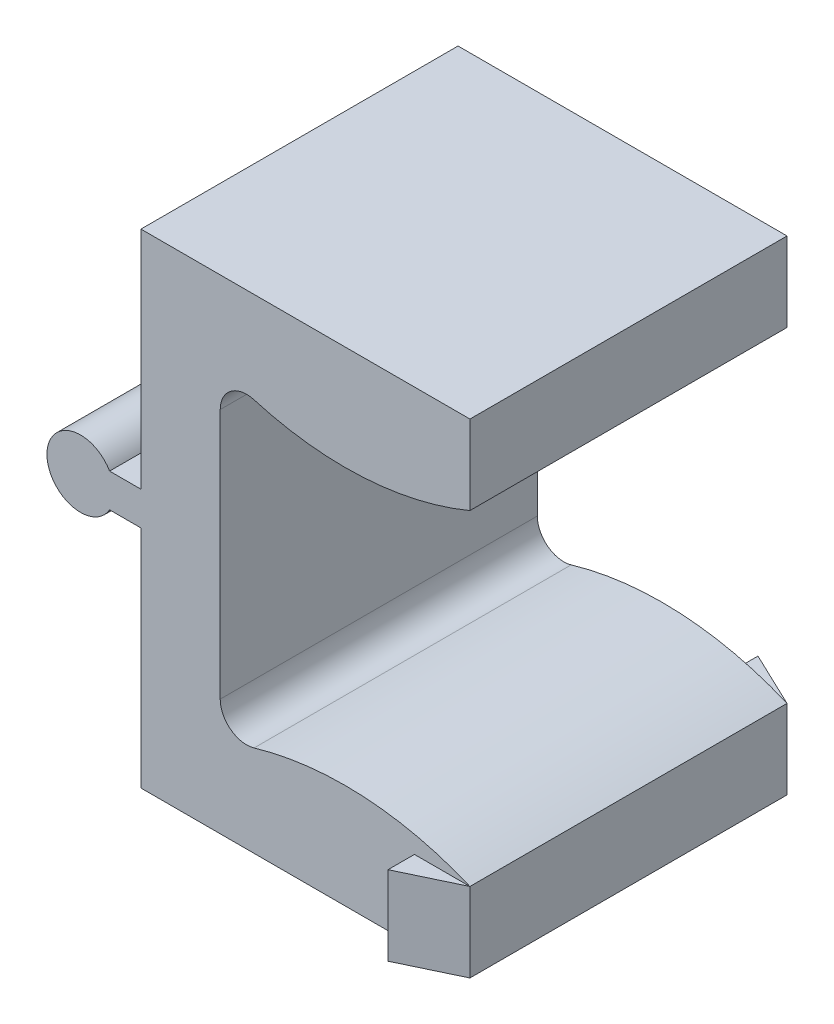
SolidWorks part; units mm, degrees
ref_plane "Front Plane" through (0, 0, 0) normal (0, 0, 1) x (1, 0, 0)
ref_plane "Top Plane" through (0, 0, 0) normal (0, 1, 0) x (1, 0, 0)
ref_plane "Right Plane" through (0, 0, 0) normal (1, 0, 0) x (0, 0, -1)
sketch "Sketch1" plane through (0, 0, 0) normal (0, 0, 1) x (1, 0, 0)
  line L2 (-159.7982, 9.1594) -> (-172.2482, 9.1594)
  line L3 (-172.2482, 9.1594) -> (-172.2482, -9.1594)
  line L7 (-169.2482, -22.8519) -> (-169.2482, 6.1594) construction
  line L13 (-142.8048, 5.1594) -> (-142.8048, -5.1594) construction
  line L23 (-159.7982, 6.1594) -> (-159.7982, 9.1594)
  line L28 (-164.5232, 5.2094) -> (-144.5007, 5.2094) construction
  line L30 (-169.2482, 6.1594) -> (-169.2482, 5.1594)
  line L34 (-169.2482, 5.1594) -> (-169.2482, -5.1594)
  line L35 (-172.2482, 0) -> (-169.2482, 0) construction
  line L36 (-169.2482, -6.1594) -> (-169.2482, -5.1594)
  line L37 (-159.7982, -6.1594) -> (-159.7982, -9.1594)
  line L38 (-159.7982, -9.1594) -> (-172.2482, -9.1594)
  arc A5 (-169.2482, 6.1594) -> (-159.7982, 6.1594) centre (-164.5232, 17.4347) ccw
  arc A6 (-169.2482, -6.1594) -> (-159.7982, -6.1594) centre (-164.5232, -17.4347) cw
  point P30 (-142.8048, 0)
  dimension "D6" = 12.2253
  dimension "D4" = 3
  dimension "D3" = 3
  dimension "D2" = 1
  dimension "D1" = 18.3188
  dimension "D5" = 12.45
extrude "MainBody" add sketch "Sketch1" along normal mid plane 12
sketch "Sketch3" plane through (0, -9.1594, 0) normal (0, -1, 0) x (1, 0, 0)
  line L0 (-159.7982, -6) -> (-161.8982, -7)
  line L1 (-161.8982, -7) -> (-161.8982, -6)
  line L2 (-172.2482, -6) -> (-159.7982, -6) construction
  line L3 (-161.8982, -6) -> (-159.7982, -6)
  line L5 (8.8033, 0) -> (-8.8033, 0) construction
  line L6 (-161.8982, 6) -> (-159.7982, 6)
  line L7 (-161.8982, 7) -> (-161.8982, 6)
  line L8 (-159.7982, 6) -> (-161.8982, 7)
  dimension "D1" = 2.1
  dimension "D2" = 1
extrude "Hook" add sketch "Sketch3" against normal up to vertex (3 mm away) up to point (-159.7982, -6.1594, -6)
fillet "Fillet2" radius 1 2 edges at (-169.2482, 6.1594, 0) (-169.2482, -6.1594, 0)
sketch "Sketch5" [suppressed] plane through (-172.2482, 0, 0) normal (-1, 0, 0) x (0, 0, 1)
  line L1 (-6, 9.1594) -> (6, 9.1594)
  line L2 (-6, 9.1594) -> (-6, -9.1594)
  line L3 (-6, -9.1594) -> (6, -9.1594)
  line L4 (6, 9.1594) -> (6, -9.1594)
extrude "Boss-Extrude1" [suppressed] add sketch "Sketch5" along normal blind 15
sketch "Sketch6" [suppressed] plane through (0, 9.1594, 0) normal (0, 1, 0) x (1, 0, 0)
  line L0 (-187.2482, -6) -> (-187.2482, 6) construction
  circle A0 centre (-182.2482, 0) radius 3.302
  dimension "D1" = 6.604
  dimension "D2" = 5
extrude "Cut-Extrude2" [suppressed] cut sketch "Sketch6" against normal through all
sketch "Sketch7" plane through (-172.2482, 0, 0) normal (-1, 0, 0) x (0, 0, 1)
  circle A0 centre (0, 0) radius 38.1
  dimension "D1" = 76.2
extrude "Boss-Extrude2" [suppressed] add sketch "Sketch7" along normal blind 5
fillet "Fillet3" [suppressed] radius 1
sketch "Sketch8" plane through (0, 0, 6) normal (0, 0, 1) x (1, 0, 0)
  line L6 (-172.2482, -0.635) -> (-173.4343, -0.635)
  line L8 (-172.2482, 0.635) -> (-173.4343, 0.635)
  line L10 (-172.2482, 0.635) -> (-173.4343, 0.635)
  line L11 (-172.2482, 0.635) -> (-172.2482, -0.635)
  line L12 (-161.8982, -9.1594) -> (-161.8982, -6.1594)
  line L14 (-169.2482, -4.7448) -> (-169.2482, 4.7448)
  line L15 (-159.7982, 6.1594) -> (-159.7982, 9.1594)
  line L16 (-159.7982, 9.1594) -> (-172.2482, 9.1594)
  line L17 (-172.2482, 9.1594) -> (-172.2482, -9.1594)
  line L18 (-172.2482, -9.1594) -> (-161.8982, -9.1594)
  line L21 (-169.2482, -4.7448) -> (-169.2482, 4.7448)
  line L22 (-159.7982, 6.1594) -> (-159.7982, 9.1594)
  line L23 (-159.7982, 9.1594) -> (-172.2482, 9.1594)
  line L24 (-172.2482, 9.1594) -> (-172.2482, -9.1594)
  line L25 (-172.2482, -9.1594) -> (-161.8982, -9.1594)
  line L26 (-172.2482, -0.635) -> (-173.4343, -0.635)
  line L32 (-161.8982, -9.1594) -> (-161.8982, -6.1594)
  line L33 (-161.8982, -6.1594) -> (-159.7982, -6.1594)
  line L34 (-161.8982, -6.1594) -> (-159.7982, -6.1594)
  arc A0 (-173.4343, 0.635) -> (-173.4343, -0.635) centre (-174.5342, 0) ccw
  arc A4 (-159.7982, -6.1594) -> (-167.9665, -5.7043) centre (-164.5232, -17.4347) ccw
  arc A6 (-169.2482, -4.7448) -> (-167.9665, -5.7043) centre (-168.2482, -4.7448) ccw
  arc A7 (-167.9665, 5.7043) -> (-159.7982, 6.1594) centre (-164.5232, 17.4347) ccw
  arc A8 (-159.7982, -6.1594) -> (-167.9665, -5.7043) centre (-164.5232, -17.4347) ccw
  arc A11 (-167.9665, 5.7043) -> (-159.7982, 6.1594) centre (-164.5232, 17.4347) ccw
  arc A12 (-169.2482, -4.7448) -> (-167.9665, -5.7043) centre (-168.2482, -4.7448) ccw
  arc A13 (-167.9665, 5.7043) -> (-169.2482, 4.7448) centre (-168.2482, 4.7448) ccw
  arc A14 (-167.9665, 5.7043) -> (-169.2482, 4.7448) centre (-168.2482, 4.7448) ccw
  point P6 (-172.2482, 0)
  line M14 (-172.2482, 9.1594) -> (-172.2482, -9.1594)
  dimension "D2" = 1.27
  dimension "D1" = 0
  dimension "D3" = 2.286
extrude "Slot" add sketch "Sketch8" against normal up to surface (12 mm away) contours L8 A0 L6 M14 region at (-174.164, 0, 6) up to face at (-165.6835, -0.5599, -6)
sketch "Sketch10" [suppressed] plane through (0, 0, -6) normal (0, 0, -1) x (-1, 0, 0)
  line L0 (166.0232, -9.1594) -> (172.2482, -9.1594)
  line L3 (172.2482, -9.1594) -> (166.0232, -9.1594)
  line L5 (172.2482, -9.1594) -> (187.9767, -44.4861)
  line L6 (195.4932, -61.3685) -> (192.3182, -61.3685)
  line L7 (159.7982, -6.1594) -> (159.7982, -9.1594)
  line L8 (159.7982, -6.1594) -> (159.7982, -9.1594)
  line L9 (159.7982, -9.1594) -> (172.2482, -9.1594)
  line L10 (172.2482, -9.1594) -> (172.2482, 9.1594)
  line L11 (172.2482, 9.1594) -> (159.7982, 9.1594)
  line L12 (159.7982, 9.1594) -> (159.7982, 6.1594)
  line L13 (169.2482, 6.1594) -> (169.2482, -6.1594)
  line L16 (159.7982, -9.1594) -> (172.2482, -9.1594)
  line L17 (172.2482, -9.1594) -> (172.2482, 9.1594)
  line L18 (172.2482, 9.1594) -> (159.7982, 9.1594)
  line L19 (159.7982, 9.1594) -> (159.7982, 6.1594)
  line L20 (169.2482, 6.1594) -> (169.2482, -6.1594)
  line L21 (195.4932, -61.3685) -> (201.8432, -61.3685)
  line L22 (201.8432, -61.3685) -> (201.8432, -59.781)
  line L24 (192.666, -55.0185) -> (200.9772, -55.0185)
  line L25 (169.0732, -9.1594) -> (192.3182, -61.3685)
  line L28 (201.8432, -59.781) -> (194.7864, -59.781)
  line L31 (193.3728, -56.606) -> (200.9772, -56.606)
  line L42 (200.9772, -55.0185) -> (200.9772, -56.606)
  line L43 (187.9767, -44.4861) -> (195.4932, -61.3685)
  arc A4 (169.2482, -6.1594) -> (159.7982, -6.1594) centre (164.5232, -17.4347) ccw
  arc A5 (159.7982, 6.1594) -> (169.2482, 6.1594) centre (164.5232, 17.4347) ccw
  arc A8 (169.2482, -6.1594) -> (159.7982, -6.1594) centre (164.5232, -17.4347) ccw
  arc A9 (159.7982, 6.1594) -> (169.2482, 6.1594) centre (164.5232, 17.4347) ccw
  dimension "D5" = 6.35
  dimension "D7" = 3.175
  dimension "D8" = 3.175
  dimension "D2" = 57.15
  dimension "D10" = 1.5875
  dimension "D13" = 114
  dimension "D14" = 114
  dimension "D3" = 1.5875
  dimension "D4" = 3.175
extrude "Boss-Extrude3" [suppressed] add sketch "Sketch10" against normal up to surface (12 mm away) up to face at (-167.7502, -0.4106, 6)
sketch "Sketch11" [suppressed] plane through (0, 0, -6) normal (0, 0, -1) x (-1, 0, 0)
  line L0 (159.7982, -9.1594) -> (159.7982, 9.1594)
  line L11 (169.2482, 6.1594) -> (169.2482, -6.1594)
  line L12 (159.7982, -6.1594) -> (159.7982, -9.1594)
  line L13 (159.7982, -9.1594) -> (169.0732, -9.1594)
  line L14 (169.0732, -9.1594) -> (192.3182, -61.3685)
  line L15 (192.3182, -61.3685) -> (201.8432, -61.3685)
  line L16 (201.8432, -61.3685) -> (201.8432, -59.781)
  line L17 (201.8432, -59.781) -> (194.7864, -59.781)
  line L18 (194.7864, -59.781) -> (193.3728, -56.606)
  line L19 (172.2482, -9.1594) -> (172.2482, 9.1594)
  line L20 (172.2482, 9.1594) -> (159.7982, 9.1594)
  line L21 (159.7982, 9.1594) -> (159.7982, 6.1594)
  line L22 (169.2482, 6.1594) -> (169.2482, -6.1594)
  line L23 (159.7982, -6.1594) -> (159.7982, -9.1594)
  line L24 (159.7982, -9.1594) -> (169.0732, -9.1594)
  line L25 (169.0732, -9.1594) -> (192.3182, -61.3685)
  line L26 (192.3182, -61.3685) -> (201.8432, -61.3685)
  line L27 (201.8432, -61.3685) -> (201.8432, -59.781)
  line L28 (201.8432, -59.781) -> (194.7864, -59.781)
  line L29 (194.7864, -59.781) -> (193.3728, -56.606)
  line L30 (172.2482, -9.1594) -> (172.2482, 9.1594)
  line L31 (172.2482, 9.1594) -> (159.7982, 9.1594)
  line L32 (159.7982, 9.1594) -> (159.7982, 6.1594)
  line L37 (193.3728, -56.606) -> (200.9772, -56.606)
  line L38 (193.3728, -56.606) -> (200.9772, -56.606)
  line L39 (200.9772, -56.606) -> (200.9772, -55.0185)
  line L40 (200.9772, -56.606) -> (200.9772, -55.0185)
  line L41 (192.666, -55.0185) -> (172.2482, -9.1594)
  line L42 (192.666, -55.0185) -> (172.2482, -9.1594)
  line L44 (200.9772, -55.0185) -> (192.666, -55.0185)
  line L45 (200.9772, -55.0185) -> (192.666, -55.0185)
  arc A2 (159.7982, 6.1594) -> (169.2482, 6.1594) centre (164.5232, 17.4347) ccw
  arc A3 (169.2482, -6.1594) -> (159.7982, -6.1594) centre (164.5232, -17.4347) ccw
  arc A4 (159.7982, 6.1594) -> (169.2482, 6.1594) centre (164.5232, 17.4347) ccw
  arc A5 (169.2482, -6.1594) -> (159.7982, -6.1594) centre (164.5232, -17.4347) ccw
  dimension "D1" = 0
extrude "Boss-Extrude4" [suppressed] add sketch "Sketch11" against normal up to surface (12 mm away) up to face at (-167.7502, -0.4106, 6)
sketch "Sketch12" [suppressed] plane through (0, 0, -6) normal (0, 0, -1) x (-1, 0, 0)
  line L0 (159.7982, -9.1594) -> (159.7982, -5.9844)
  line L1 (159.7982, -5.9844) -> (162.0842, -5.9844)
  line L3 (162.0842, -5.2351) -> (159.7982, -5.2351)
  line L4 (162.0842, -5.2351) -> (162.0842, -6.7337)
  line L5 (162.0842, -6.7337) -> (159.7982, -6.7337)
  line L6 (159.7982, -5.2351) -> (159.7982, -6.7337)
  line L7 (162.0842, -5.2351) -> (159.7982, -6.7337) construction
  line L8 (162.0842, -6.7337) -> (159.7982, -5.2351) construction
  line L9 (172.2482, 9.1594) -> (159.7982, 9.1594)
  line L10 (159.7982, 9.1594) -> (159.7982, -9.1594)
  line L11 (159.7982, -9.1594) -> (169.0732, -9.1594)
  line L12 (169.0732, -9.1594) -> (192.3182, -61.3685)
  line L13 (192.3182, -61.3685) -> (201.8432, -61.3685)
  line L14 (201.8432, -61.3685) -> (201.8432, -59.781)
  line L15 (201.8432, -59.781) -> (194.7864, -59.781)
  line L16 (194.7864, -59.781) -> (193.3728, -56.606)
  line L17 (172.2482, -9.1594) -> (172.2482, 9.1594)
  line L18 (172.2482, 9.1594) -> (159.7982, 9.1594)
  line L19 (159.7982, 9.1594) -> (159.7982, -9.1594)
  line L20 (159.7982, -9.1594) -> (169.0732, -9.1594)
  line L21 (169.0732, -9.1594) -> (192.3182, -61.3685)
  line L22 (192.3182, -61.3685) -> (201.8432, -61.3685)
  line L23 (201.8432, -61.3685) -> (201.8432, -59.781)
  line L24 (201.8432, -59.781) -> (194.7864, -59.781)
  line L25 (194.7864, -59.781) -> (193.3728, -56.606)
  line L26 (172.2482, -9.1594) -> (172.2482, 9.1594)
  line L38 (193.3728, -56.606) -> (200.9772, -56.606)
  line L39 (193.3728, -56.606) -> (200.9772, -56.606)
  line L40 (200.9772, -56.606) -> (200.9772, -55.0185)
  line L42 (192.666, -55.0185) -> (172.2482, -9.1594)
  line L43 (192.666, -55.0185) -> (172.2482, -9.1594)
  line L45 (200.9772, -56.606) -> (200.9772, -55.0185)
  line L46 (200.9772, -55.0185) -> (192.666, -55.0185)
  line L47 (200.9772, -55.0185) -> (192.666, -55.0185)
  circle A0 centre (162.0842, -5.9844) radius 1.3843
  point P8 (160.9412, -5.9844)
  dimension "D4" = 2.7686
  dimension "D2" = 3.175
  dimension "D3" = 2.286
  dimension "D5" = 1.4986
extrude "Cut-Extrude3" [suppressed] cut sketch "Sketch12" against normal up to surface (12 mm away) up to face at (-167.7502, -0.4106, 6)
pattern_linear "LPattern1" [suppressed] count 4 spacing 4.28 of bodies 117
sketch "Sketch15" [suppressed] plane through (0, 0, 6) normal (0, 0, 1) x (1, 0, 0)
  line L1 (-172.2482, -9.1594) -> (-179.8682, -9.1594)
  line L2 (-172.2482, -9.1594) -> (-172.2482, 67.0406)
  line L3 (-172.2482, 67.0406) -> (-179.8682, 67.0406)
  line L4 (-179.8682, -9.1594) -> (-179.8682, 67.0406)
  dimension "D1" = 7.62
  dimension "D2" = 76.2
extrude "Boss-Extrude6" [suppressed] add sketch "Sketch15" against normal up to surface (12 mm away) up to face at (-167.7502, -0.4106, -6)
sketch "Sketch16" [suppressed] plane through (0, 0, 6) normal (0, 0, 1) x (1, 0, 0)
  line L0 (-172.2482, 9.1594) -> (-172.2482, 67.0406) construction
  line L1 (-172.2482, 63.8656) -> (-174.5342, 63.8656)
  line L2 (-172.2482, 63.8656) -> (-172.2482, 62.367)
  line L3 (-172.2482, 62.367) -> (-174.5342, 62.367)
  line L4 (-174.5342, 63.8656) -> (-174.5342, 62.367)
  line L5 (-172.2482, 67.0406) -> (-179.8682, 67.0406) construction
  circle A0 centre (-174.5342, 63.1163) radius 1.2814
  line M12 (-172.2482, 9.1594) -> (-172.2482, 67.0406)
  dimension "D4" = 2.5629
  dimension "D1" = 3.175
  dimension "D2" = 1.4986
  dimension "D3" = 2.286
extrude "Cut-Extrude6" [suppressed] cut sketch "Sketch16" against normal up to surface (12 mm away) contours A0 L3 L1 M12 | L3 A0 L1 L4 | L1 A0 L3 L4 up to face at (-167.7502, -0.4106, -6)
pattern_linear "LPattern3" [suppressed] count 10 spacing 5.08 of bodies 124
fillet "Fillet5" [suppressed] radius 2.54
equation "\"HookThickness\"= 3mm"
equation "\"D3@Sketch1\"=\"HookThickness\""
equation "\"D4@Sketch1\"=\"HookThickness\""
equation "\"CylinderDiameter\"=3"
equation "\"D1@Sketch7\"=\"CylinderDiameter\""
equation "\"Mount Tolerance\"= .005in"
equation "\"Mount Thickness\"= .0625in"
equation "\"Mount Angle\"= 114"
equation "\"D14@Sketch10\"=\"Mount Angle\""
equation "\"D13@Sketch10\"= \"Mount Angle\""
equation "\"Joint Radius\"= .05in"
equation "\"Joint Thickness\"= .05in"
equation "\"Joint Tolerance\"= .009in"
equation "\"D4@Sketch12\"= (\"Joint Radius\" * 2) + \"Joint Tolerance\""
equation "\"D5@Sketch12\"= \"Joint Thickness\" + \"Joint Tolerance\""
